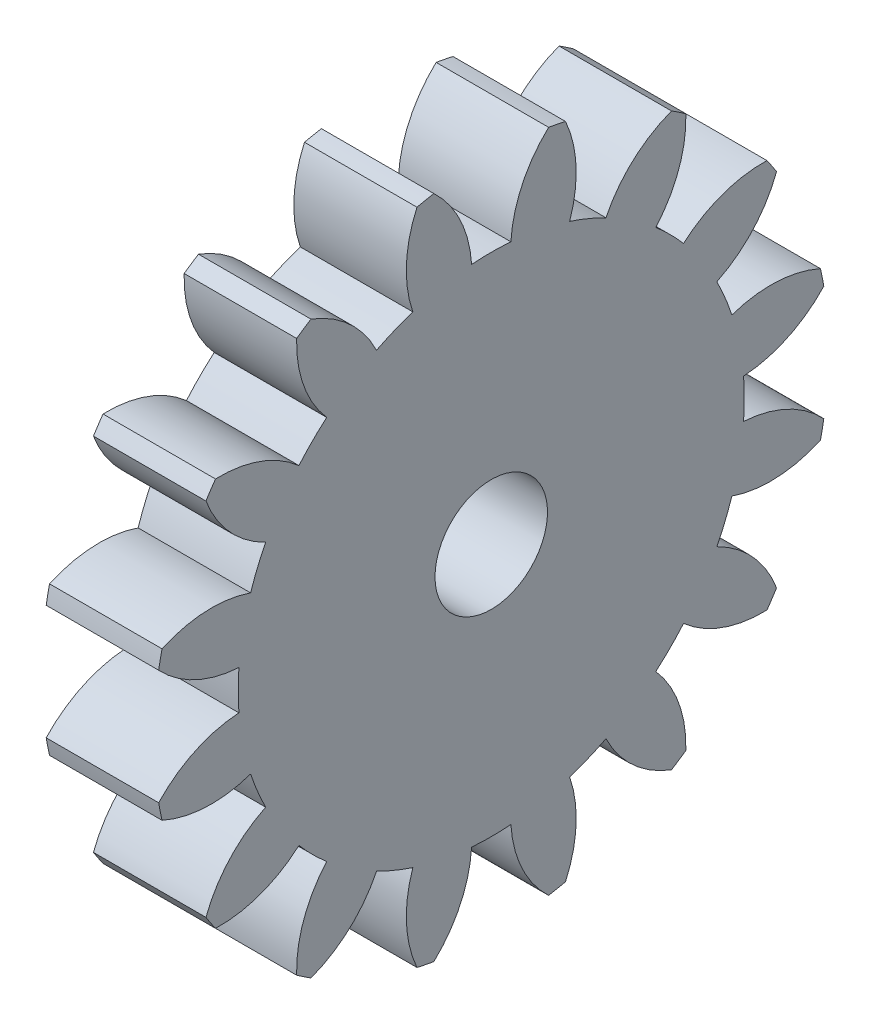
SolidWorks part; units mm, degrees
ref_plane "Plane1" through (0, 0, 0) normal (0, 0, 1) x (1, 0, 0)
ref_plane "Plane2" through (0, 0, 0) normal (0, 1, 0) x (1, 0, 0)
ref_plane "Plane3" through (0, 0, 0) normal (1, 0, 0) x (0, 0, -1)
sketch "HoldingSke" plane through (0, 0, 0) normal (0, 1, 0) x (1, 0, 0)
  line L0 (0, 0) -> (0.9613, -0.2756)
  line L1 (-15, 0) -> (100, 0) construction
  line L2 (0, 0) -> (-2.1039, 2.3779)
  line L3 (0, 0) -> (-11.863, 4.5341)
  line L4 (0, 0) -> (8.3015, 2.3804)
  line L5 (0, 0) -> (-14.0543, -5.2418)
  line L6 (0, 0) -> (-2.4869, -1.6779)
  line L7 (-2.1039, 2.3779) -> (1.1249, 17.0263)
  line L8 (-76.2, 54.61) -> (-75.7, 54.61)
  line L9 (-71.009, 38.7566) -> (-53.1078, 45.2721)
  line L10 (-76.2, 71.12) -> (104.1128, 71.12)
  line L11 (0, 0) -> (-3, 0)
  line L12 (-76.2, 101.6) -> (-76.162, 101.6)
  line L13 (24.9733, 27.94) -> (52.9518, 28.4284)
  line L14 (24.9733, 27.94) -> (24.9743, 27.94)
  line L15 (24.9733, 27.94) -> (100.4006, 29.5858)
  line L16 (-63.627, -1) -> (-12.827, -1)
  circle A0 centre (0, 0) radius 1.5
  circle A1 centre (0, 0) radius 2.5
  circle A2 centre (0, 0) radius 2.5
  circle A3 centre (0, 0) radius 1.5
  dimension "MHD" = 5
  dimension "Hub_dia" = 5
  dimension "Bore" = 3
  dimension "MBD" = 3
  dimension "Num_teeth" = 16
  dimension "Pitch_radius" = 180.3128
  dimension "Pitch" = 1
  dimension "Width" = 3
  dimension "Overall_len" = 15
  dimension "Show_teeth" = 16
  dimension "Thickness" = 3
  dimension "OAL" = 15.0001
  dimension "T_dim" = 0.5
  dimension "Ap" = 20
  dimension "H" = 19.05
  dimension "Backlash" = 0.038
  dimension "Addendum_fac" = 1
  dimension "Dedendum_fac" = 1.25
  dimension "Clearance_fac" = 0.25
  dimension "Dedendum_add" = 0.001
  dimension "Module" = 1
sketch "BasProSke" plane through (0, 0, 0) normal (0, 1, 0) x (1, 0, 0)
  line L0 (-10, 0) -> (60, 0) construction
  line L1 (0, 0) -> (0, 9)
  line L2 (0, 0) -> (3, 0)
  line L3 (3, 0) -> (3, 9)
  line L4 (3, 9) -> (0, 9)
  dimension "Diameter" = 18
  dimension "Thickness" = 3
revolve "Base-Revolve" add sketch "BasProSke" angle 360 about L0
sketch "TooCutSke" plane through (0, 0, 0) normal (1, 0, 0) x (0, 0, -1)
  line L1 (0, 0) -> (0, 107) construction
  line L2 (0, 0) -> (-0.8506, 7.9547) construction
  line L3 (0, 0) -> (-3.1089, 15.6293) construction
  line L4 (-0.8506, 7.9547) -> (-1.5544, 7.8146) construction
  arc A0 (0.5238, 6.7286) -> (-0.5238, 6.7286) centre (0, 0) ccw
  arc A1 (1.5534, 8.8907) -> (-1.5534, 8.8907) centre (0, 0) ccw
  circle A2 centre (0, 0) radius 8 construction
  circle A3 centre (0, 0) radius 7.5175 construction
  arc A4 (-0.5238, 6.7286) -> (-1.5534, 8.8907) centre (-3.7179, 6.5338) ccw
  arc A5 (1.5534, 8.8907) -> (0.5238, 6.7286) centre (3.7179, 6.5338) ccw
  dimension "Root_dia" = 13.498
  dimension "Overcut_dia" = 18.0508
  dimension "Pitch_dia" = 16
  dimension "Base_dia" = 15.0351
  dimension "Flank_rad" = 3.2
  dimension "Half_ang" = 11.25
  dimension "Half_CT" = 0.7176
extrude "ToothCut" cut sketch "TooCutSke" along normal through all
fillet "Breaks" [suppressed] radius 0.02 tangent propagation no
fillet "RootFillets" [suppressed] radius 0.251
pattern_circular "TeethCuts" count 16 every 22.5 about axis through (-10, 0, 0) along (1, 0, 0) of "ToothCut", "RootFillets", "Breaks"
sketch "HubNeaOneSke" plane through (0, 0, 0) normal (-1, 0, 0) x (0, 0, 1)
  circle A0 centre (0, 0) radius 2.5
  dimension "Diameter" = 5
extrude "HubNearOne" [suppressed] add sketch "HubNeaOneSke" along normal blind 12.0001
sketch "HubNeaBotSke" plane through (0, 0, 0) normal (-1, 0, 0) x (0, 0, 1)
  circle A0 centre (0, 0) radius 2.5
  dimension "Diameter" = 5
extrude "HubNearBoth" [suppressed] add sketch "HubNeaBotSke" along normal blind 6
ref_plane "FarPln" through (3, 0, 0) normal (1, 0, 0) x (0, 0, -1)
sketch "HubFarSke" plane through (3, 0, 0) normal (1, 0, 0) x (0, 0, -1)
  circle A0 centre (0, 0) radius 2.5
  dimension "Diameter" = 5
extrude "HubFar" [suppressed] add sketch "HubFarSke" along normal blind 6
sketch "BorSke" plane through (0, 0, 0) normal (1, 0, 0) x (0, 0, -1)
  circle A0 centre (0, 0) radius 1.5
  dimension "Diameter" = 3
extrude "Bore" cut sketch "BorSke" along normal mid plane 30.0001
sketch "KeySke" plane through (0, 0, 0) normal (1, 0, 0) x (0, 0, -1)
  line L0 (-0.6, 0) -> (-0.6, 2)
  line L1 (-0.6, 2) -> (0.6, 2)
  line L2 (0.6, 2) -> (0.6, 0)
  line L3 (0, 0) -> (0, 34) construction
  line L4 (-0.6, 0) -> (0.6, 0)
  dimension "Offset" = 2
  dimension "Width" = 1.2
extrude "Keyway" [suppressed] cut sketch "KeySke" along normal mid plane 30.0001
pattern_circular "Keyway2" [suppressed] count 2 every 90 about axis through (-10, 0, 0) along (1, 0, 0)
equation "' \"Module@HoldingSke\" = 6.35"
equation "' \"Num_teeth@HoldingSke\" = 12"
equation "' \"Ap@HoldingSke\" =  20"
equation "' \"Width@HoldingSke\" = 0.5 * 25.4"
equation "' \"Hub_dia@HoldingSke\"= 1 * 25.4"
equation "' \"Overall_len@HoldingSke\" = 1.0 * 25.4"
equation "' \"Bore@HoldingSke\" = 0.75 * 25.4"
equation "' \"T_dim@HoldingSke\" = 0.1 * 25.4"
equation "' \"Width@KeySke\" = 0.25 * 25.4"
equation "' \"Show_teeth@HoldingSke\" = 13"
equation "' \"Backlash@HoldingSke\" = 0.009 * 25.4"
equation "' \"Addendum_fac@HoldingSke\" = 1.0"
equation "' \"Dedendum_fac@HoldingSke\" = 1.25"
equation "' \"Dedendum_add@HoldingSke\" = 0.00005 * 25.4"
equation "' \"Clearance_fac@HoldingSke\" = 0.25"
equation "\"Pitch@HoldingSke\" = 1 / \"Module@HoldingSke\""
equation "\"Overcut_dia@TooCutSke\" = (\"Num_teeth@HoldingSke\" + 2 * \"Addendum_fac@HoldingSke\") / \"Pitch@HoldingSke\" + 0.002 * 25.4"
equation "\"Pitch_dia@TooCutSke\" = \"Num_teeth@HoldingSke\" / \"Pitch@HoldingSke\""
equation "\"Base_dia@TooCutSke\" = \"Num_teeth@HoldingSke\" / \"Pitch@HoldingSke\" * cos((\"Ap@HoldingSke\"  * 3.14159265 / 180))"
equation "\"Root_dia@TooCutSke\" = (\"Num_teeth@HoldingSke\" + 2) / \"Pitch@HoldingSke\" - 2 * (\"Addendum_fac@HoldingSke\" + \"Dedendum_fac@HoldingSke\") / \"Pitch@HoldingSke\" - \"Dedendum_add@HoldingSke\" * 2"
equation "\"Half_ang@TooCutSke\" = 180 / \"Num_teeth@HoldingSke\""
equation "\"Half_CT@TooCutSke\" = \"Num_teeth@HoldingSke\" / \"Pitch@HoldingSke\" * sin((3.14159265 / 2 / \"Num_teeth@HoldingSke\")) / 2 - 7 * \"Backlash@HoldingSke\" / 4"
equation "\"Flank_rad@TooCutSke\" = \"Num_teeth@HoldingSke\" / \"Pitch@HoldingSke\" / 5"
equation "\"Radius@RootFillets\" = \"Clearance_fac@HoldingSke\" / \"Pitch@HoldingSke\" + \"Dedendum_add@HoldingSke\""
equation "\"Break_rad@Breaks\" = 0.02 / \"Pitch@HoldingSke\""
equation "\"Thickness@HoldingSke\" = \"Width@HoldingSke\""
equation "\"OAL@HoldingSke\" = \"Thickness@HoldingSke\""
equation "\"MHD@HoldingSke\" = (\"Num_teeth@HoldingSke\" + 2) / \"Pitch@HoldingSke\" - 2 * (\"Addendum_fac@HoldingSke\" + \"Dedendum_fac@HoldingSke\")  / \"Pitch@HoldingSke\" - \"Dedendum_add@HoldingSke\" * 2"
equation "\"MBD@HoldingSke\" = (\"Num_teeth@HoldingSke\" + 2) / \"Pitch@HoldingSke\" - 2 * (\"Addendum_fac@HoldingSke\" + \"Dedendum_fac@HoldingSke\")  / \"Pitch@HoldingSke\" - \"Dedendum_add@HoldingSke\" * 2 - 0.002 * 25.4"
equation "\"MHD@HoldingSke\" = ((sgn( \"MHD@HoldingSke\" - \"Hub_dia@HoldingSke\" )-1)*( \"MHD@HoldingSke\" - \"Hub_dia@HoldingSke\" ))/-2+ \"Hub_dia@HoldingSke\""
equation "\"MBD@HoldingSke\" = ((sgn( \"MBD@HoldingSke\" - \"Bore@HoldingSke\" )-1)*( \"MBD@HoldingSke\" - \"Bore@HoldingSke\" ))/-2+ \"Bore@HoldingSke\""
equation "\"OAL@HoldingSke\" = ((sgn( \"OAL@HoldingSke\" - \"Overall_len@HoldingSke\" )+1)*( \"OAL@HoldingSke\" - \"Overall_len@HoldingSke\" ))/2 + \"Overall_len@HoldingSke\" + 0.000002 * 25.4"
equation "\"Num_teeth@TeethCuts\" = int( \"Show_teeth@HoldingSke\" ) + 1"
equation "\"Num_teeth@TeethCuts\" = ((sgn( \"Num_teeth@TeethCuts\" - \"Num_teeth@HoldingSke\" )-1)*( \"Num_teeth@TeethCuts\" - \"Num_teeth@HoldingSke\" ))/-2+ \"Num_teeth@HoldingSke\""
equation "\"Num_teeth@TeethCuts\" = ((sgn( \"Num_teeth@TeethCuts\" - 2.0)+1)*( \"Num_teeth@TeethCuts\" - 2.0))/2 +2.0"
equation "\"Angle@TeethCuts\" = 360.0 / \"Num_teeth@HoldingSke\""
equation "\"Diameter@BasProSke\" = (\"Num_teeth@HoldingSke\" + 2 * \"Addendum_fac@HoldingSke\") / \"Pitch@HoldingSke\""
equation "\"Thickness@BasProSke\"  = \"Thickness@HoldingSke\""
equation "' \"Fillet_rad@BasProSke\" =  \"Thickness@HoldingSke\" * 0.05"
equation "\"MHD@HoldingSke\" = ((sgn( \"MHD@HoldingSke\" - \"Root_dia@TooCutSke\" )-1)*( \"MHD@HoldingSke\" - \"Root_dia@TooCutSke\" ))/-2+ \"Root_dia@TooCutSke\""
equation "\"Diameter@HubNeaOneSke\" = \"MHD@HoldingSke\""
equation "\"Length@HubNearOne\" = \"OAL@HoldingSke\" - \"Thickness@BasProSke\""
equation "\"Diameter@HubNeaBotSke\" = \"MHD@HoldingSke\""
equation "\"Length@HubNearBoth\" = ( \"OAL@HoldingSke\" - \"Thickness@BasProSke\" ) / 2.0"
equation "\"Thickness@FarPln\" = \"Thickness@BasProSke\""
equation "\"Diameter@HubFarSke\" = \"MHD@HoldingSke\""
equation "\"Length@HubFar\" = ( \"OAL@HoldingSke\" - \"Thickness@BasProSke\" ) / 2.0"
equation "\"Diameter@BorSke\" = \"MBD@HoldingSke\""
equation "\"D1@Bore\" = \"OAL@HoldingSke\" * 2.0"
equation "\"D1@Keyway\" = \"OAL@HoldingSke\" * 2.0"
equation "\"Offset@KeySke\" = \"T_dim@HoldingSke\" + \"MBD@HoldingSke\" / 2.0"
